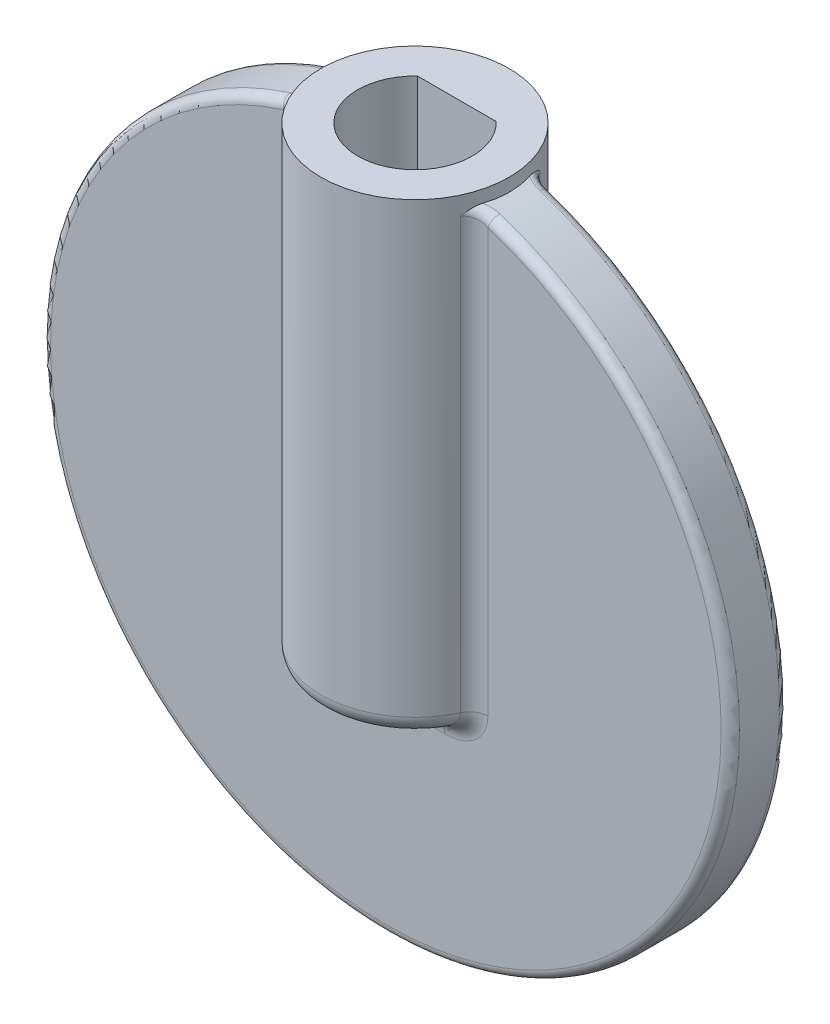
SolidWorks part; units mm, degrees
ref_plane "Front Plane" through (0, 0, 0) normal (0, 0, 1) x (1, 0, 0)
ref_plane "Top Plane" through (0, 0, 0) normal (0, 1, 0) x (1, 0, 0)
ref_plane "Right Plane" through (0, 0, 0) normal (1, 0, 0) x (0, 0, -1)
sketch "Sketch1" plane through (0, 0, 0) normal (0, 1, 0) x (1, 0, 0)
  line L0 (-2.1424, 2.275) -> (2.1424, 2.275) construction
  circle A0 centre (0, 0) radius 5.125
  circle A1 centre (0, 0) radius 3.125 construction
  arc A2 (-2.1424, 2.275) -> (2.1424, 2.275) centre (0, 0) ccw construction
  point P6 (0, -3.125)
  dimension "D1" = 6.25
  dimension "D2" = 2
  dimension "D3" = 5.4
extrude "Boss-Extrude1" add sketch "Sketch1" against normal blind 25.4
ref_plane "Plane1" through (0, 0, 0) normal (0, 1, 0) x (1, 0, 0)
sketch "Sketch2" plane through (0, 0, 0) normal (0, 0, 1) x (1, 0, 0)
  line L0 (5.6375, 0) -> (-5.6375, 0) construction
  circle A0 centre (0, -18.75) radius 18.75
  dimension "D1" = 37.5
extrude "Boss-Extrude2" add sketch "Sketch2" along normal mid plane 3.175
sketch "Sketch3" plane through (0, 0, 0) normal (0, 1, 0) x (1, 0, 0)
  line L0 (-2.1424, 2.275) -> (2.1424, 2.275) construction
  line L1 (-2.1424, 2.275) -> (2.1424, 2.275)
  circle A0 centre (0, 0) radius 3.125 construction
  arc A1 (-2.1424, 2.275) -> (2.1424, 2.275) centre (0, 0) ccw
extrude "Cut-Extrude1" cut sketch "Sketch3" against normal blind 12
fillet "Fillet1" radius 1 8 edges at (0, -25.4, 1.5875) (0, -25.4, -1.5875) (4.8729, -13.0221, 1.5875) (0, -25.4, 5.125) (-4.8729, -13.0221, 1.5875) (0, -25.4, -5.125) (4.8729, -13.0221, -1.5875) (-4.8729, -13.0221, -1.5875)
fillet "Fillet2" radius 0.5 6 edges at (-5.0998, -0.7069, -1.6954) (4.9082, -0.6538, -1.822) (-4.9082, -0.6538, 1.822) (5.0998, -0.7069, 1.6954) (0, -37.5, -1.5875) (0, -37.5, 1.5875)
